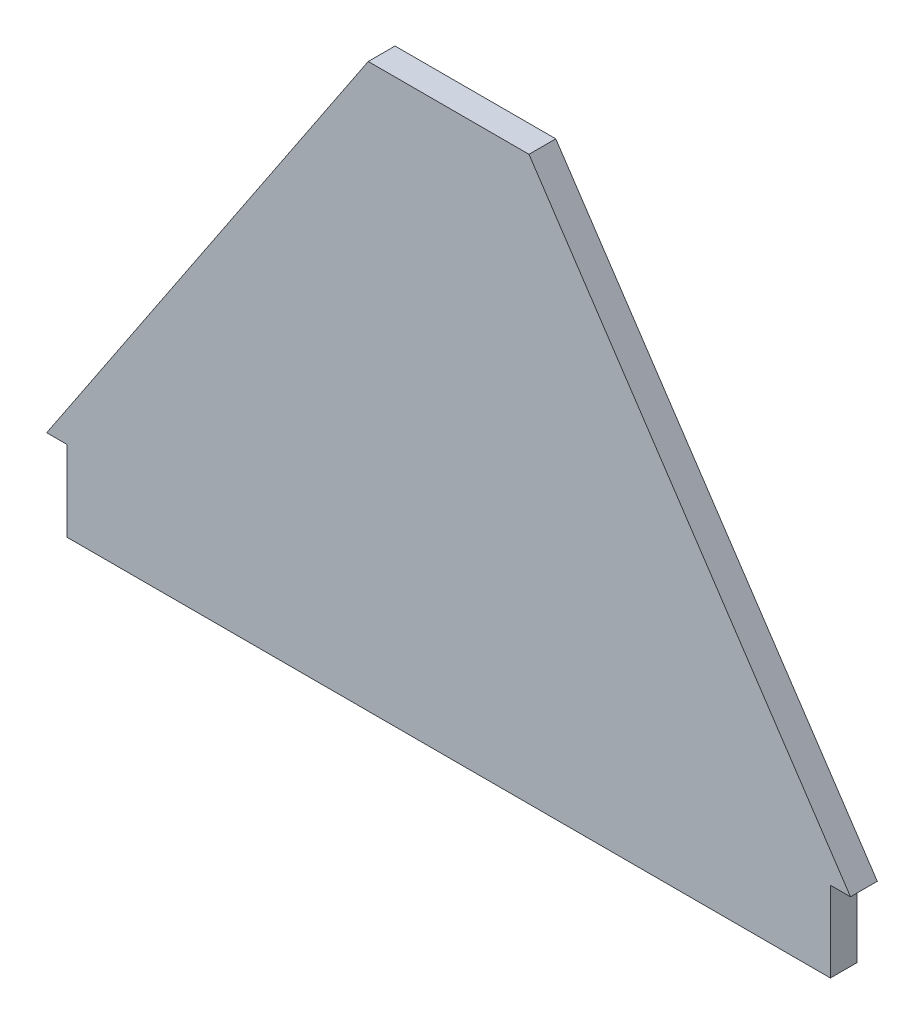
SolidWorks part; units mm, degrees
material "Balsa"
ref_plane "Front Plane" through (0, 0, 0) normal (0, 0, 1) x (1, 0, 0)
ref_plane "Top Plane" through (0, 0, 0) normal (0, 1, 0) x (1, 0, 0)
ref_plane "Right Plane" through (0, 0, 0) normal (1, 0, 0) x (0, 0, -1)
sketch "Sketch1" plane through (0, 0, 0) normal (0, 0, 1) x (1, 0, 0)
  line L0 (75, 11.7259) -> (71.25, 11.7259)
  line L1 (0, -3.2741) -> (0, 101.7259) construction
  line L2 (15, 101.7259) -> (-15, 101.7259)
  line L3 (-75, 11.7259) -> (-15, 101.7259)
  line L4 (75, 11.7259) -> (15, 101.7259)
  line L5 (71.25, 11.7259) -> (71.25, -3.2741)
  line L6 (71.25, -3.2741) -> (-71.25, -3.2741)
  line L7 (-71.25, -3.2741) -> (-71.25, 11.7259)
  line L8 (-71.25, 11.7259) -> (-75, 11.7259)
  point P3 (0, -3.2741)
  point P4 (0, 0)
  point P10 (0, 101.7259)
  dimension "D1" = 30
  dimension "D2" = 90
  dimension "D3" = 75
  dimension "D4" = 75
  dimension "D5" = 142.5
  dimension "D6" = 15
extrude "Boss-Extrude1" add sketch "Sketch1" along normal blind 5
